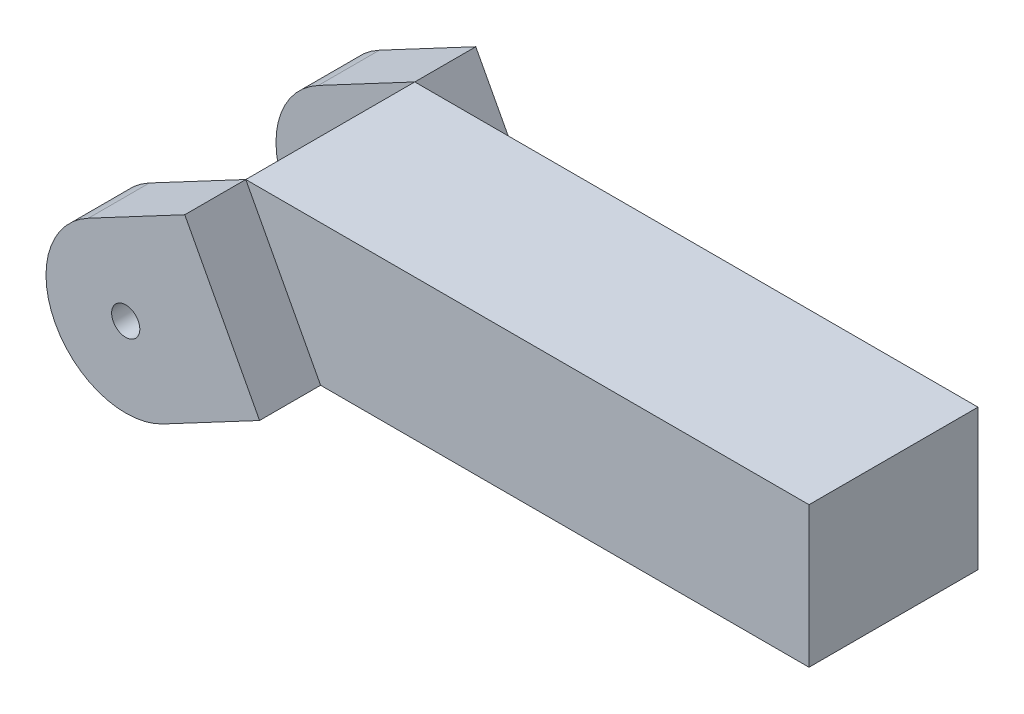
SolidWorks part; units mm, degrees
ref_plane "前视基准面" through (0, 0, 0) normal (0, 0, 1) x (1, 0, 0)
ref_plane "上视基准面" through (0, 0, 0) normal (0, 1, 0) x (1, 0, 0)
ref_plane "右视基准面" through (0, 0, 0) normal (1, 0, 0) x (0, 0, -1)
sketch "草图1" plane through (0, 0, 0) normal (0, 0, 1) x (1, 0, 0)
  line L1 (-60, 15) -> (60, 15)
  line L2 (-60, 15) -> (-60, -15)
  line L3 (-60, -15) -> (60, -15)
  line L4 (60, 15) -> (60, -15)
  line L5 (-60, 15) -> (60, -15) construction
  line L6 (-60, -15) -> (60, 15) construction
  point P0 (0, 0)
  dimension "D1" = 30
  dimension "D2" = 120
extrude "凸台-拉伸1" add sketch "草图1" along normal blind 36
sketch "草图2" plane through (0, 0, 0) normal (0, 0, -1) x (-1, 0, 0)
  line L0 (-60, 15) -> (60, 15) construction
  line L1 (-55, 10) -> (-14, 10)
  line L2 (-55, 10) -> (-55, -11)
  line L3 (-55, -11) -> (-14, -11)
  line L4 (-14, 10) -> (-14, -11)
  line L5 (-60, -15) -> (-60, 15) construction
  dimension "D1" = 5
  dimension "D2" = 5
  dimension "D3" = 41
  dimension "D4" = 21
extrude "切除-拉伸1" cut sketch "草图2" against normal blind 30 contours L1 L4 L3 L2
sketch "草图3" plane through (0, 0, 0) normal (0, 0, -1) x (-1, 0, 0)
  line L0 (-83.9789, 0) -> (77.6219, 0) construction
ref_plane "基准面1" through (0, 0, -13) normal (0, 0, -1) x (-1, 0, 0)
sketch "草图4" plane through (0, 0, -13) normal (0, 0, -1) x (-1, 0, 0)
  line L0 (60, 15) -> (44.0635, -15)
  line L1 (60, 15) -> (80.549, 4.0841)
  line L2 (44.0635, -15) -> (64.6125, -25.9159)
  line L4 (60, 15) -> (60, -15) construction
  line L5 (-60, 15) -> (60, 15) construction
  arc A0 (64.6125, -25.9159) -> (80.549, 4.0841) centre (72.5807, -10.9159) ccw
  circle A1 centre (72.5807, -10.9159) radius 3
  dimension "D1" = 6
extrude "凸台-拉伸2" add sketch "草图4" against normal up to surface (13 mm away) up to face at (34.5, -0.5, 0)
ref_plane "基准面2" through (0, 0, 18) normal (0, 0, -1) x (-1, 0, 0)
mirror "镜向5" about plane through (0, 0, 18) normal (0, 0, -1) of bodies 112
sketch "草图6" plane through (-3.4832, 6.557, 0) normal (0.4691, -0.8831, 0) x (0.8831, 0.4691, 0)
  line L1 (-45.9507, 0) -> (-69.2191, 0)
  line L2 (-45.9507, 0) -> (-45.9507, 36)
  line L3 (-45.9507, 36) -> (-69.2191, 36)
  line L4 (-69.2191, 0) -> (-69.2191, 36)
extrude "切除-拉伸2" cut sketch "草图6" against normal through all
